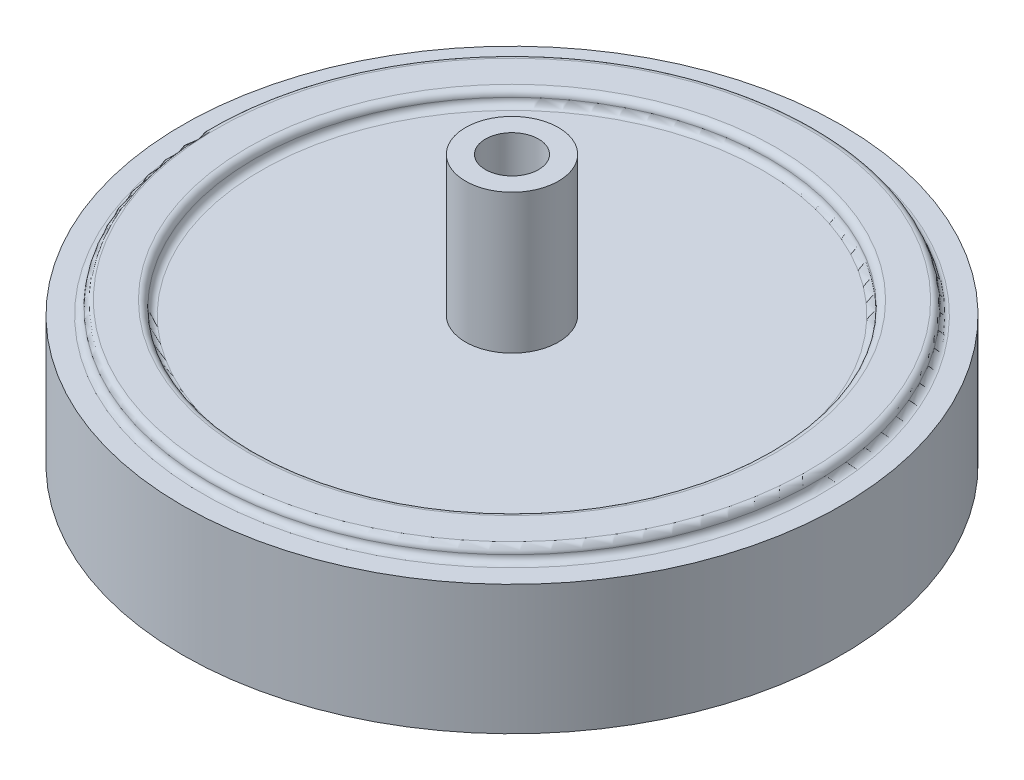
SolidWorks part; units mm, degrees
ref_plane "Front Plane" through (0, 0, 0) normal (0, 0, 1) x (1, 0, 0)
ref_plane "Top Plane" through (0, 0, 0) normal (0, 1, 0) x (1, 0, 0)
ref_plane "Right Plane" through (0, 0, 0) normal (1, 0, 0) x (0, 0, -1)
sketch "Sketch1" plane through (0, 0, 0) normal (0, 1, 0) x (1, 0, 0)
  circle A0 centre (0, 0) radius 3.5
  circle A1 centre (0, 0) radius 2
  dimension "D1" = 7
  dimension "D2" = 4
extrude "Boss-Extrude1" add sketch "Sketch1" along normal blind 10.5
sketch "Sketch2" plane through (0, 0, 0) normal (0, -1, 0) x (1, 0, 0)
  circle A0 centre (0, 0) radius 24.825
  dimension "D1" = 49.65
extrude "Boss-Extrude2" add sketch "Sketch2" along normal blind 10.5
sketch "Sketch3" plane through (0, -10.5, 0) normal (0, -1, 0) x (1, 0, 0)
  circle A0 centre (0, 0) radius 22
  dimension "D1" = 44
extrude "Cut-Extrude1" cut sketch "Sketch3" against normal blind 9
sketch "Sketch4" plane through (0, -1.5, 0) normal (0, -1, 0) x (1, 0, 0)
  circle A0 centre (0, 0) radius 18
  dimension "D1" = 36
extrude "Boss-Extrude3" add sketch "Sketch4" along normal blind 1
sketch "Sketch5" plane through (0, -2.5, 0) normal (0, -1, 0) x (1, 0, 0)
  circle A0 centre (0, 0) radius 5
  dimension "D1" = 10
extrude "Boss-Extrude4" add sketch "Sketch5" along normal blind 4.15
sketch "Sketch6" plane through (0, -6.65, 0) normal (0, -1, 0) x (1, 0, 0)
  circle A0 centre (0, 0) radius 3.425
  dimension "D1" = 6.85
extrude "Boss-Extrude5" add sketch "Sketch6" along normal blind 8
sketch "Sketch7" plane through (0, -14.65, 0) normal (0, -1, 0) x (1, 0, 0)
  circle A0 centre (0, 0) radius 2
  dimension "D1" = 4
extrude "Cut-Extrude2" cut sketch "Sketch7" against normal up to surface (25.15 mm away) up to face at (0, 10.5, 3.5)
sketch "Sketch8" plane through (0, 0, 0) normal (0, 1, 0) x (1, 0, 0)
  circle A0 centre (0, 0) radius 22.8
  circle A1 centre (0, 0) radius 19.4
  dimension "D1" = 38.8
  dimension "D2" = 45.6
extrude "Boss-Extrude6" add sketch "Sketch8" along normal blind 1
fillet "Fillet1" radius 0.5 4 edges at (0, 1, 19.4) (0, 1, 22.8) (0, 0, 19.4) (0, 0, -22.8)
chamfer "Chamfer1" distance 0.75 angle 75 1 edges at (0, -10.5, -24.825) first distance on face at (0, -10.5, -24.825)
